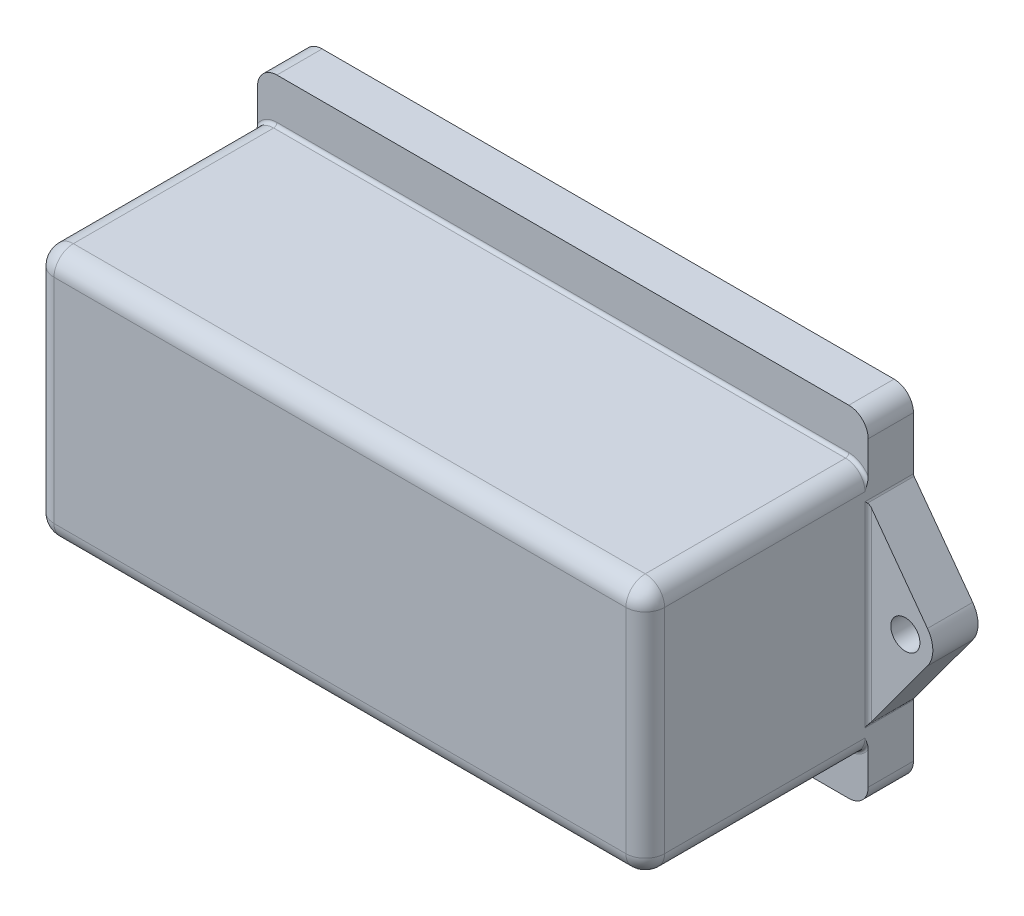
SolidWorks part; units mm, degrees
material "Custom Plastic"
ref_plane "X-Y Datum" through (0, 0, 0) normal (0, 0, 1) x (1, 0, 0)
ref_plane "X-Z Datum" through (0, 0, 0) normal (0, 1, 0) x (1, 0, 0)
ref_plane "Y-Z Datum" through (0, 0, 0) normal (1, 0, 0) x (0, 0, -1)
sketch "Sketch1" plane through (0, 0, 0) normal (0, 0, 1) x (1, 0, 0)
  line L1 (-47.25, 26.35) -> (47.25, 26.35)
  line L2 (-47.25, 26.35) -> (-47.25, -26.35)
  line L3 (-47.25, -26.35) -> (47.25, -26.35)
  line L4 (47.25, 26.35) -> (47.25, -26.35)
  line L5 (-47.25, 26.35) -> (47.25, -26.35) construction
  line L6 (-47.25, -26.35) -> (47.25, 26.35) construction
  point P0 (0, 0)
  dimension "D1" = 52.7
  dimension "D2" = 94.5
extrude "Boss-Extrude1" add sketch "Sketch1" along normal blind 7
sketch "Sketch2" plane through (0, 0, 7) normal (0, 0, 1) x (1, 0, 0)
  line L0 (-47.25, 26.35) -> (-47.25, -26.35) construction
  line L1 (-47.25, 19.5) -> (47.25, 19.5)
  line L2 (-47.25, 19.5) -> (-47.25, -19.5)
  line L3 (-47.25, -19.5) -> (47.25, -19.5)
  line L4 (47.25, 19.5) -> (47.25, -19.5)
  line L5 (-47.25, 19.5) -> (47.25, -19.5) construction
  line L6 (-47.25, -19.5) -> (47.25, 19.5) construction
  point P0 (0, 0)
  dimension "D1" = 39
extrude "Boss-Extrude2" add sketch "Sketch2" along normal blind 34.5
sketch "Sketch3" plane through (0, 0, 0) normal (0, 0, -1) x (-1, 0, 0)
  line L0 (-53, 0) -> (53, 0)
  line L1 (-47.25, 15) -> (-47.25, -15)
  line L2 (-47.25, -15) -> (-56.4246, -2.5169)
  line L3 (-47.25, 15) -> (-56.4246, 2.5169)
  line L5 (-47.25, 26.35) -> (-47.25, -26.35)
  line L6 (-47.25, -26.35) -> (47.25, -26.35)
  line L7 (47.25, -26.35) -> (47.25, 26.35)
  line L8 (47.25, 26.35) -> (-47.25, 26.35)
  line L9 (-47.25, 26.35) -> (-47.25, -26.35)
  line L10 (-47.25, -26.35) -> (47.25, -26.35)
  line L11 (47.25, -26.35) -> (47.25, 26.35)
  line L12 (47.25, 26.35) -> (-47.25, 26.35)
  circle A0 centre (-53, 0) radius 2.25
  circle A2 centre (-53, 0) radius 4.25
  point P4 (0, 0)
  point P18 (-47.25, 0)
  line M11 (-47.25, 26.35) -> (-47.25, -26.35)
  dimension "D2" = 4.5
  dimension "D1" = 106
  dimension "D5" = 30
  dimension "D3" = 2
  dimension "D4" = 0
extrude "Boss-Extrude3" add sketch "Sketch3" against normal blind 7 contours A2 L0 L3 M11 | A2 L2 L0 M11 | A2 A0 region at (51.7131, -3.9241, 0) region at (49.71, 6.7727, 0) region at (49.71, -6.7727, 0)
mirror "Mirror1" about plane through (0, 0, 0) normal (1, 0, 0) of "Boss-Extrude3"
fillet "Fillet1" radius 3 12 edges at (0, -19.5, 41.5) (-47.25, 0, 41.5) (0, 19.5, 41.5) (47.25, 0, 41.5) (-47.25, 19.5, 24.25) (47.25, 19.5, 24.25) (47.25, -19.5, 24.25) (-47.25, -19.5, 24.25) (-47.25, -26.35, 3.5) (-47.25, 26.35, 3.5) (47.25, 26.35, 3.5) (47.25, -26.35, 3.5) tangent propagation no
fillet "Fillet2" radius 0.5 12 edges at (-46.3713, -18.6213, 7) (46.3713, -18.6213, 7) (46.3713, 18.6213, 7) (-46.3713, 18.6213, 7) (0, -19.5, 7) (0, 19.5, 7) (47.25, 15, 3.5) (47.25, 0, 7) (47.25, -15, 3.5) (-47.25, 15, 3.5) (-47.25, 0, 7) (-47.25, -15, 3.5)
